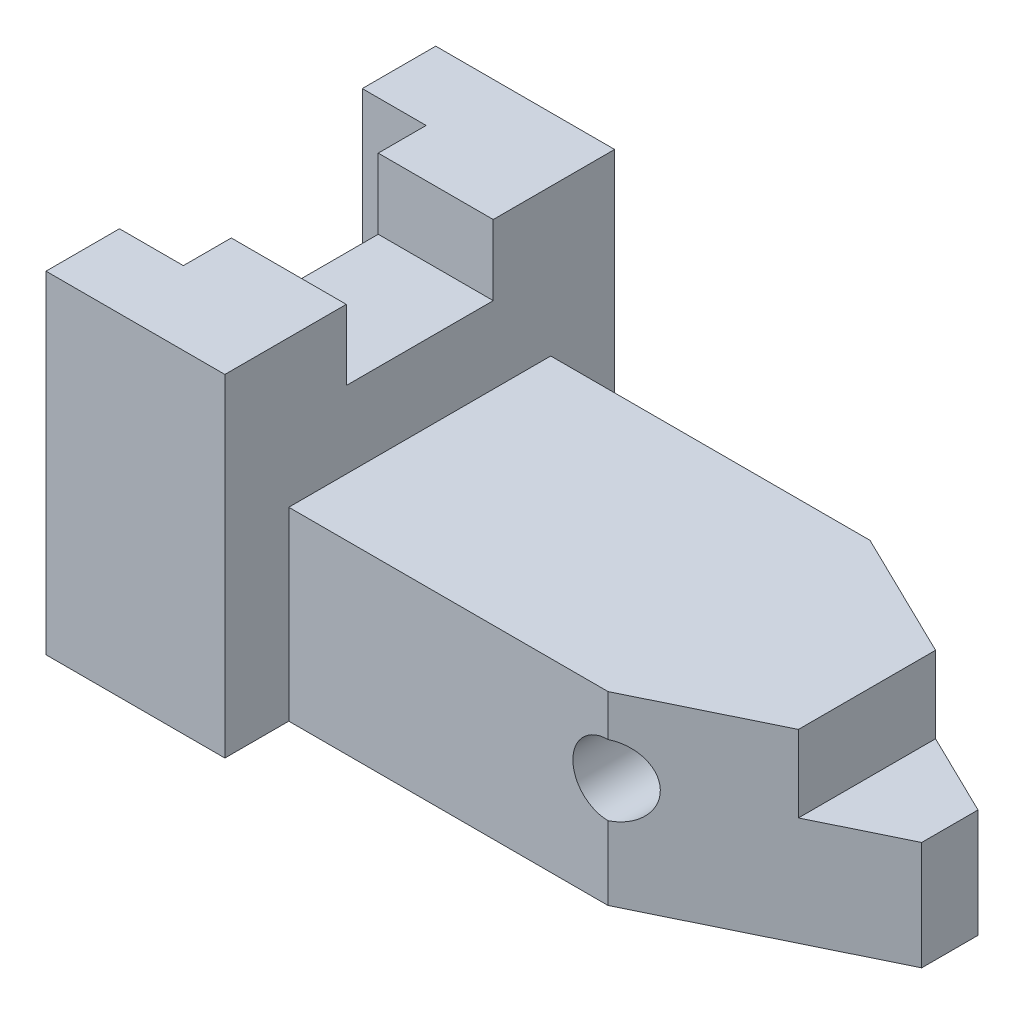
SolidWorks part; units mm, degrees
ref_plane "Front Plane" through (0, 0, 0) normal (0, 0, 1) x (1, 0, 0)
ref_plane "Top Plane" through (0, 0, 0) normal (0, 1, 0) x (1, 0, 0)
ref_plane "Right Plane" through (0, 0, 0) normal (1, 0, 0) x (0, 0, -1)
sketch "Sketch1" plane through (0, 0, 0) normal (0, 1, 0) x (1, 0, 0)
  line L0 (10, 0) -> (120, 0) construction
  line L1 (120, 0) -> (10, 0) construction
  line L2 (0, 19) -> (0, 37.2272) construction
  line L3 (0, -19) -> (0, -30.5)
  line L4 (0, 30.5) -> (28, 30.5)
  line L5 (0, 30.5) -> (0, 19)
  line L6 (0, -30.5) -> (28, -30.5)
  line L7 (28, 30.5) -> (28, -30.5)
  line L8 (28, 20.5) -> (77.9688, 20.5)
  line L9 (28, 20.5) -> (28, -20.5)
  line L10 (28, -20.5) -> (77.9688, -20.5)
  line L12 (0, -19) -> (10, -19)
  line L13 (110.9688, 4.4048) -> (110.9688, -4.4048)
  line L14 (98, -10.7301) -> (98, 10.7301)
  line L15 (110.9688, -4.4048) -> (77.9688, -20.5)
  line L16 (110.9688, 4.4048) -> (77.9688, 20.5)
  line L18 (0, 19) -> (10, 19)
  line L19 (10, -19) -> (10, 19)
  line L21 (10, 11.5) -> (28, 11.5)
  line L22 (10, 11.5) -> (10, -11.5)
  line L23 (10, -11.5) -> (28, -11.5)
  line L24 (28, 11.5) -> (28, -11.5)
  point P21 (120, 0)
  dimension "D1" = 28
  dimension "D2" = 120
  dimension "D3" = 52
  dimension "D4" = 41
  dimension "D5" = 33
  dimension "D6" = 22
  dimension "D7" = 61
  dimension "D8" = 38
  dimension "D9" = 10
  dimension "D10" = 23
extrude "Boss-Extrude1" add sketch "Sketch1" along normal blind 17 contours L23 L19 L12 L3 L6 L7 | L19 L23 L9 L21 | L19 L21 L7 L4 L5 L18 | L14 L16 L8 L7 L9 L10 L15 | L13 L16 L14 L15 region at (15.477, 0, 21.9437) region at (19, 0, 0) region at (60.9274, 0, 0) region at (15.477, 0, -21.9437) region at (103.5811, 0, 0)
extrude "Boss-Extrude2" add sketch "Sketch1<3>" along normal blind 29 contours L19 L21 L7 L4 L5 L18 | L19 L23 L9 L21 | L23 L19 L12 L3 L6 L7 | L14 L16 L8 L7 L9 L10 L15 region at (15.477, 0, 21.9437) region at (19, 0, 0) region at (60.9274, 0, 0) region at (15.477, 0, -21.9437)
sketch "Sketch1<3>" plane through (0, 0, 0) normal (0, 1, 0) x (1, 0, 0) same geometry as "Sketch1"
extrude "Boss-Extrude3" add sketch "Sketch1<4>" along normal blind 41 contours L19 L21 L7 L4 L5 L18 | L19 L23 L9 L21 | L23 L19 L12 L3 L6 L7 region at (15.477, 0, 21.9437) region at (19, 0, 0) region at (15.477, 0, -21.9437)
sketch "Sketch1<4>" plane through (0, 0, 0) normal (0, 1, 0) x (1, 0, 0) same geometry as "Sketch1"
extrude "Boss-Extrude4" add sketch "Sketch1<5>" along normal blind 52 contours L23 L19 L12 L3 L6 L7 | L19 L21 L7 L4 L5 L18 region at (15.477, 0, 21.9437) region at (15.477, 0, -21.9437)
sketch "Sketch1<5>" plane through (0, 0, 0) normal (0, 1, 0) x (1, 0, 0) same geometry as "Sketch1"
sketch "Sketch2" plane through (0, 0, 20.5) normal (0, 0, 1) x (1, 0, 0)
  line L0 (77.9688, 29) -> (77.9688, 0) construction
  line L2 (110.9688, 17) -> (98, 17) construction
  circle A0 centre (77.9688, 17) radius 5.5
  point P4 (0, 0)
  dimension "D1" = 11
extrude "Cut-Extrude1" cut sketch "Sketch2" against normal through all
